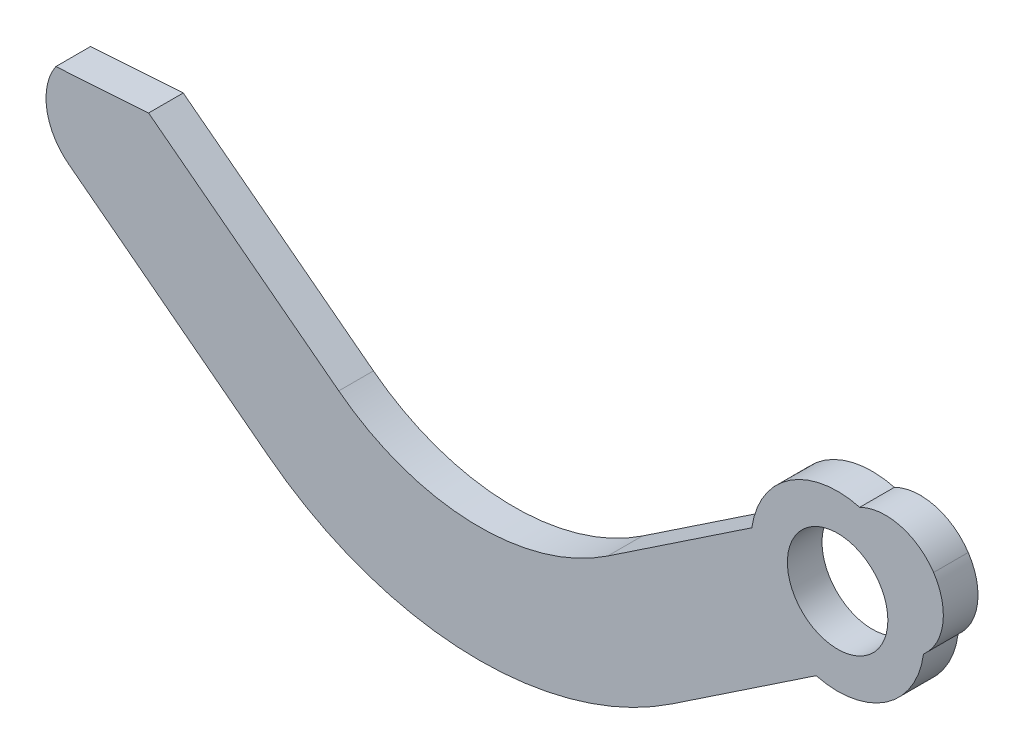
SolidWorks part; units mm, degrees
ref_plane "Plan de face" through (0, 0, 0) normal (0, 0, 1) x (1, 0, 0)
ref_plane "Plan de dessus" through (0, 0, 0) normal (0, 1, 0) x (1, 0, 0)
ref_plane "Plan de droite" through (0, 0, 0) normal (1, 0, 0) x (0, 0, -1)
sketch "Esquisse1" plane through (0, 0, 0) normal (0, 0, 1) x (1, 0, 0)
  line L0 (0, 0) -> (-70, 0) construction
  line L1 (-70, 0) -> (-48.7197, -16.2905)
  line L2 (-25.4362, -17.029) -> (0, 0)
  circle A0 centre (-70, 0) radius 5
  circle A1 centre (0, 0) radius 5
  arc A2 (-48.7197, -16.2905) -> (-25.4362, -17.029) centre (-36.5625, -0.4096) ccw
  point P8 (-37.3425, -25)
  dimension "D2" = 10
  dimension "D4" = 25
  dimension "D5" = 20
  dimension "D3" = 10
  dimension "D1" = 70
extrude "Extru.-Mince1" add sketch "Esquisse1" along normal blind 3 thin contours L1 A2 L2 thin type one direction wall 10
fillet "Congé1" radius 5 3 edges at (-76.0786, -7.9405, 1.5) (5.5632, -8.3097, 1.5) (0, 0, 1.5)
sketch "Esquisse2" plane through (0, 0, 3) normal (0, 0, 1) x (1, 0, 0)
  line L0 (-19.873, -25.3387) -> (1.4083, -11.0913) construction
  circle A0 centre (-5.5281, -9.718) radius 7.5
  dimension "D1" = 10
  dimension "D2" = 15
  dimension "D3" = 5
extrude "Boss.-Extru.1" add sketch "Esquisse2" against normal blind 3
sketch "Esquisse3" plane through (0, 0, 3) normal (0, 0, 1) x (1, 0, 0)
  circle A0 centre (-5.5281, -9.718) radius 4.35
  point P0 (-5.5281, -9.718)
  dimension "D1" = 8.7
extrude "Enlèv. mat.-Extru.1" cut sketch "Esquisse3" against normal blind 6
sketch "Esquisse4" plane through (0, 0, 3) normal (0, 0, 1) x (1, 0, 0)
  line L0 (-73.23, -4.2194) -> (-65.1864, -3.6849)
  line L1 (-73.0393, -3.9702) -> (-70, 0) construction
  line L2 (-70, 0) -> (-48.7197, -16.2905) construction
  line L3 (-65.1864, -3.6849) -> (-70, 0)
  line L4 (-70, 0) -> (-73.23, -4.2194)
  line L5 (-20.1213, -0.6905) -> (-137.3827, -8.482) construction
extrude "Enlèv. mat.-Extru.2" cut sketch "Esquisse4" against normal blind 10
